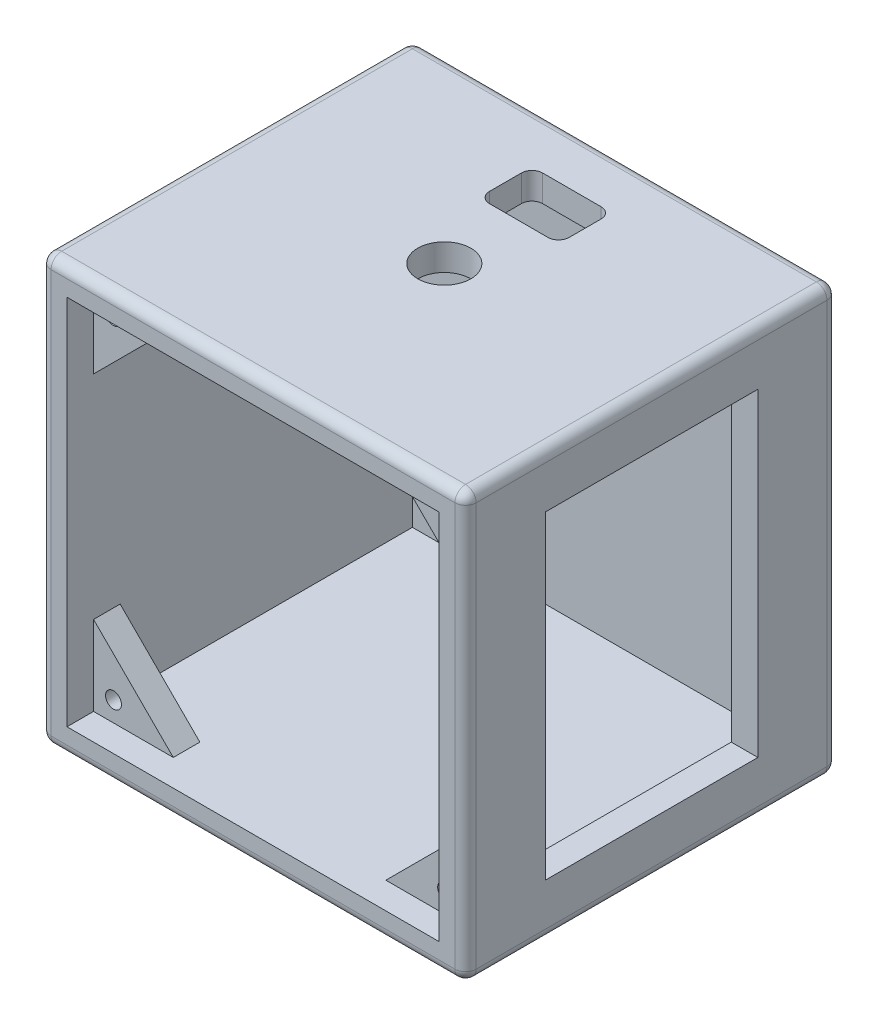
SolidWorks part; units mm, degrees
ref_plane "Спереди" through (0, 0, 0) normal (0, 0, 1) x (1, 0, 0)
ref_plane "Сверху" through (0, 0, 0) normal (0, 1, 0) x (1, 0, 0)
ref_plane "Справа" through (0, 0, 0) normal (1, 0, 0) x (0, 0, -1)
other "Configuration Table"
sketch "Эскиз1" plane through (0, 0, 0) normal (0, 0, 1) x (1, 0, 0)
  line L1 (40, -40) -> (-40, -40)
  line L2 (40, -40) -> (40, 40)
  line L3 (40, 40) -> (-40, 40)
  line L4 (-40, -40) -> (-40, 40)
  line L5 (40, -40) -> (-40, 40) construction
  line L6 (40, 40) -> (-40, -40) construction
  point P0 (0, 0)
  dimension "D1" = 80
  dimension "D2" = 80
extrude "Бобышка-Вытянуть1" add sketch "Эскиз1" along normal blind 70
sketch "Эскиз2" plane through (0, 0, 70) normal (0, 0, 1) x (1, 0, 0)
  line L0 (40, 40) -> (-40, 40) construction
  line L1 (35, -35) -> (-35, -35)
  line L2 (35, -35) -> (35, 35)
  line L3 (35, 35) -> (-35, 35)
  line L4 (-35, -35) -> (-35, 35)
  line L5 (35, -35) -> (-35, 35) construction
  line L6 (35, 35) -> (-35, -35) construction
  line L7 (40, -40) -> (40, 40) construction
  point P0 (0, 0)
  dimension "D1" = 5
  dimension "D2" = 5
extrude "Вырез-Вытянуть1" cut sketch "Эскиз2" against normal blind 65
fillet "Скругление1" radius 2 2 edges at (-40, -40, 35) (-40, 40, 35)
fillet "Скругление2" radius 2 7 edges at (1, -40, 0) (-39.4142, -39.4142, 0) (-40, 0, 0) (-39.4142, 39.4142, 0) (40, 0, 0) (40, 40, 35) (1, 40, 0)
fillet "Скругление3" radius 2 2 edges at (39.4142, -39.4142, 0.5858) (40, -40, 36)
sketch "Эскиз3" plane through (0, 40, 0) normal (0, 1, 0) x (1, 0, 0)
  line L0 (0, 0) -> (0, -46.1034) construction
  line L1 (38, -2) -> (-38, -2) construction
  line L2 (5.5, -20) -> (-5.5, -20)
  line L3 (7.5, -18) -> (7.5, -12)
  line L4 (5.5, -10) -> (-5.5, -10)
  line L5 (-7.5, -18) -> (-7.5, -12)
  line L6 (7.5, -20) -> (-7.5, -10) construction
  line L7 (7.5, -10) -> (-7.5, -20) construction
  arc A0 (7.5, -18) -> (5.5, -20) centre (5.5, -18) cw
  arc A1 (-7.5, -18) -> (-5.5, -20) centre (-5.5, -18) ccw
  arc A2 (7.5, -12) -> (5.5, -10) centre (5.5, -12) ccw
  arc A3 (-5.5, -10) -> (-7.5, -12) centre (-5.5, -12) ccw
  point P3 (0, -15)
  dimension "D4" = 2
  dimension "D1" = 8
  dimension "D2" = 15
  dimension "D3" = 10
extrude "Вырез-Вытянуть3" cut sketch "Эскиз3" against normal blind 10
sketch "Эскиз4" plane through (40, 0, 0) normal (1, 0, 0) x (0, 0, -1)
  line L0 (-70, 38) -> (-2, -38) construction
  line L1 (-2, 38) -> (-70, -38) construction
  line L3 (-31, -15) -> (-41, -15)
  line L4 (-31, -15) -> (-31, 15)
  line L5 (-31, 15) -> (-41, 15)
  line L6 (-41, -15) -> (-41, 15)
  line L7 (-31, -15) -> (-41, 15) construction
  line L8 (-31, 15) -> (-41, -15) construction
  point P8 (-36, 0)
  dimension "D1" = 10
  dimension "D2" = 30
extrude "Вырез-Вытянуть4" cut sketch "Эскиз4" against normal blind 10
sketch "Эскиз5" plane through (0, 40, 0) normal (0, 1, 0) x (1, 0, 0)
  line L0 (0, -2) -> (0, -34) construction
  line L1 (38, -2) -> (-38, -2) construction
  line L2 (-5.5, -20) -> (5.5, -20) construction
  circle A0 centre (0, -34) radius 5
  dimension "D1" = 10
  dimension "D2" = 14
extrude "Вырез-Вытянуть5" cut sketch "Эскиз5" against normal blind 10
fillet "Скругление4" radius 2 8 edges at (39.4142, -39.4142, 70) (-39.4142, -39.4142, 70) (-39.4142, 39.4142, 70) (39.4142, 39.4142, 70) (0, 40, 70) (-40, 0, 70) (0, -40, 70) (40, 0, 70)
sketch "Эскиз6" plane through (40, 0, 0) normal (1, 0, 0) x (0, 0, -1)
  line L0 (-68, 38) -> (-2, -38) construction
  line L1 (-2, -38) -> (-2, 38) construction
  line L2 (-68, -38) -> (-2, -38) construction
  line L3 (-2, 38) -> (-68, -38) construction
  line L5 (-15, -30) -> (-55, -30)
  line L6 (-15, -30) -> (-15, 30)
  line L7 (-15, 30) -> (-55, 30)
  line L8 (-55, -30) -> (-55, 30)
  line L9 (-15, -30) -> (-55, 30) construction
  line L10 (-15, 30) -> (-55, -30) construction
  point P11 (-35, 0)
  dimension "D1" = 60
  dimension "D2" = 40
extrude "Вырез-Вытянуть6" cut sketch "Эскиз6" against normal blind 10
sketch "Эскиз7" plane through (0, 0, 5) normal (0, 0, 1) x (1, 0, 0)
  line L0 (-20, 35) -> (-35, 20)
  line L1 (35, 35) -> (-35, 35) construction
  line L2 (-35, 35) -> (-35, -35) construction
  line L3 (-20, 35) -> (-35, 35)
  line L4 (-35, 35) -> (-35, 20)
  line L5 (-35, 35) -> (-27.5, 27.5) construction
  line L6 (0, 35) -> (0, -35) construction
  line L7 (35, 35) -> (-35, 35) construction
  line L8 (-35, -35) -> (35, -35) construction
  line L9 (35, 0) -> (-35, 0) construction
  line L10 (35, -35) -> (35, 35) construction
  line L11 (35, 20) -> (20, 35)
  line L12 (35, 20) -> (35, 35)
  line L13 (35, 35) -> (20, 35)
  line L14 (35, 35) -> (27.5, 27.5) construction
  line L15 (20, -35) -> (35, -20)
  line L16 (20, -35) -> (35, -35)
  line L17 (35, -35) -> (35, -20)
  line L18 (35, -35) -> (27.5, -27.5) construction
  line L19 (-35, -20) -> (-20, -35)
  line L20 (-35, -20) -> (-35, -35)
  line L21 (-35, -35) -> (-20, -35)
  line L22 (-35, -35) -> (-27.5, -27.5) construction
  circle A0 centre (-31.25, 31.25) radius 1.5
  circle A1 centre (31.25, 31.25) radius 1.5
  circle A2 centre (31.25, -31.25) radius 1.5
  circle A3 centre (-31.25, -31.25) radius 1.5
  point P43 (0, 0)
  dimension "D3" = 3
  dimension "D1" = 45
  dimension "D2" = 15
  dimension "D4" = 4
extrude "Бобышка-Вытянуть2" add sketch "Эскиз7" along normal blind 60
sketch "Эскиз8" plane through (0, 0, 0) normal (0, 0, -1) x (-1, 0, 0)
  line L0 (-40, -38) -> (-40, 38) construction
  line L1 (35, -35) -> (-35, -35)
  line L2 (35, -35) -> (35, 35)
  line L3 (35, 35) -> (-35, 35)
  line L4 (-35, -35) -> (-35, 35)
  line L5 (35, -35) -> (-35, 35) construction
  line L6 (35, 35) -> (-35, -35) construction
  line L7 (-38, 40) -> (38, 40) construction
  point P0 (0, 0)
  dimension "D1" = 5
  dimension "D2" = 5
extrude "Вырез-Вытянуть7" cut sketch "Эскиз8" against normal blind 60 contours L2 L1 L4 L3
sketch "Эскиз9" plane through (0, 0, 0) normal (0, 0, -1) x (-1, 0, 0)
  line L1 (35, -35) -> (-35, -35)
  line L2 (35, -35) -> (35, 35)
  line L3 (35, 35) -> (-35, 35)
  line L4 (-35, -35) -> (-35, 35)
  line L5 (35, -35) -> (-35, 35) construction
  line L6 (35, 35) -> (-35, -35) construction
  point P0 (0, 0)
extrude "Бобышка-Вытянуть3" add sketch "Эскиз9" against normal blind 5 separate body
